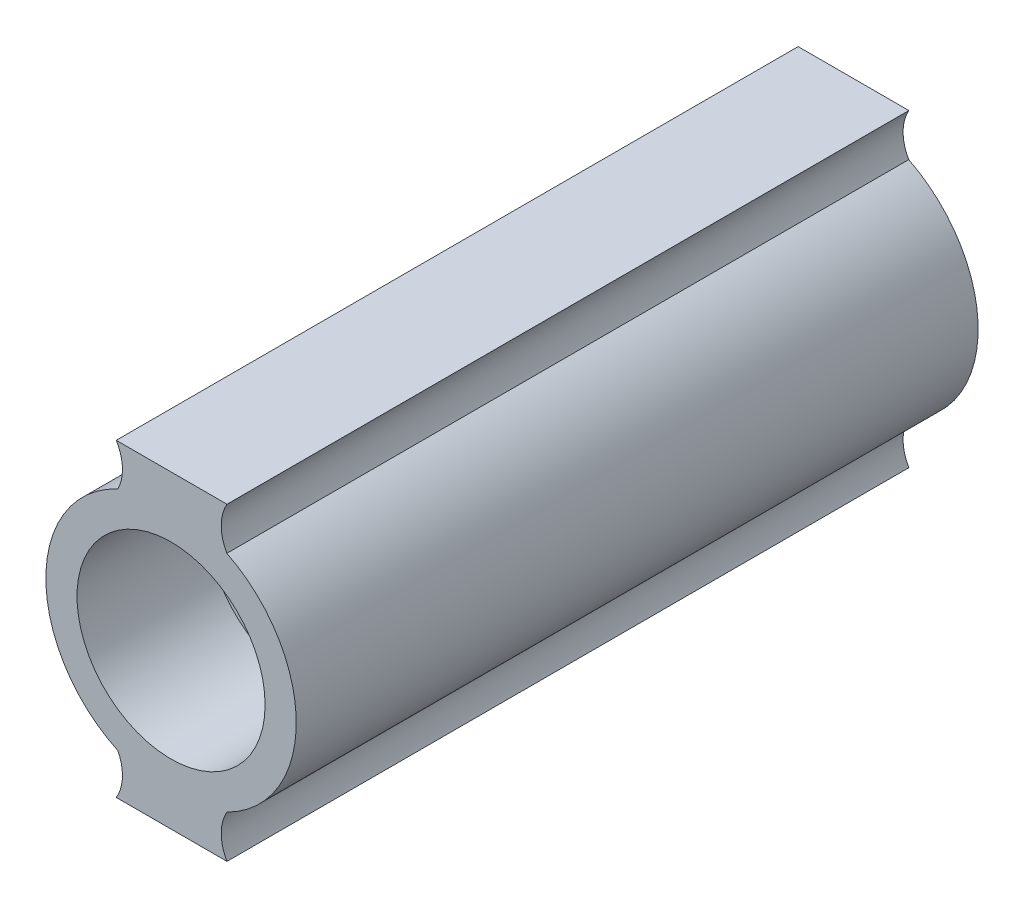
SolidWorks part; units mm, degrees
note: The reader was unsure of these and kept them because the rebuilt part matched: shared geometry of "Sketch1<3>", "Sketch1<6>", "Sketch1<7>".
material "ABS"
ref_plane "Front Plane" through (0, 0, 0) normal (0, 0, 1) x (1, 0, 0)
ref_plane "Top Plane" through (0, 0, 0) normal (0, 1, 0) x (1, 0, 0)
ref_plane "Right Plane" through (0, 0, 0) normal (1, 0, 0) x (0, 0, -1)
other "Center of Mass"
sketch "Sketch1" plane through (0, 0, 0) normal (0, 0, 1) x (1, 0, 0)
  circle A0 centre (-8.0877, 2.8885) radius 4.7625
  arc A1 (-0.1953, 6.0686) -> (-4.9075, 10.7808) centre (-8.0877, 2.8885) ccw
  arc A2 (-11.2679, 10.7808) -> (-15.9801, 6.0686) centre (-8.0877, 2.8885) ccw
  arc A3 (-15.9801, -0.2917) -> (-11.2679, -5.0039) centre (-8.0877, 2.8885) ccw
  arc A4 (-4.9075, -5.0039) -> (-0.1953, -0.2917) centre (-8.0877, 2.8885) ccw
  circle A5 centre (-8.0877, 2.8885) radius 14.0233
  circle A6 centre (-8.0877, 2.8885) radius 18.669
  circle A7 centre (-8.0877, 2.8885) radius 3.556
  ellipse E0 centre (0.2625, 2.8885) end of major axis (0.2625, -0.3246) minor radius 3.2067 (-0.1953, 6.0686) -> (-0.1953, -0.2917) ccw
  ellipse E1 centre (-8.0877, 11.2387) end of major axis (-4.8746, 11.2387) minor radius 3.2067 (-11.2679, 10.7808) -> (-4.9075, 10.7808) ccw
  ellipse E2 centre (-16.438, 2.8885) end of major axis (-16.438, 6.1016) minor radius 3.2067 (-15.9801, -0.2917) -> (-15.9801, 6.0686) ccw
  ellipse E3 centre (-8.0877, -5.4618) end of major axis (-11.3008, -5.4618) minor radius 3.2067 (-4.9075, -5.0039) -> (-11.2679, -5.0039) ccw
  ellipse E4 centre (-8.0877, -5.4618) end of major axis (-11.3008, -5.4618) minor radius 3.2067 (-11.2679, -5.0039) -> (-4.9075, -5.0039) ccw
  ellipse E5 centre (0.2625, 2.8885) end of major axis (0.2625, -0.3246) minor radius 3.2067 (-0.1953, -0.2917) -> (-0.1953, 6.0686) ccw
  ellipse E6 centre (-8.0877, 11.2387) end of major axis (-4.8746, 11.2387) minor radius 3.2067 (-4.9075, 10.7808) -> (-11.2679, 10.7808) ccw
  ellipse E7 centre (-16.438, 2.8885) end of major axis (-16.438, 6.1016) minor radius 3.2067 (-15.9801, 6.0686) -> (-15.9801, -0.2917) ccw
  dimension "D2" = 7.112
  dimension "D3" = 37.338
  dimension "D1" = 28.0467
extrude "Boss-Extrude1" add sketch "Sketch1" along normal blind 0.0025 contours E1 E6 | E2 E7 | E3 E4 | E0 E5
extrude "Boss-Extrude2" add sketch "Sketch1<3>" along normal blind 1.9812 contours E3 A4 E0 A1 E1 A2 E2 A3 A0 | A0 A7
sketch "Sketch1<3>" plane through (0, 0, 0) normal (0, 0, 1) x (1, 0, 0) same geometry as "Sketch1"
extrude "Boss-Extrude4" add sketch "Sketch1<6>" along normal blind 1.9812 contours A5 E7 A2 E6 A1 E5 A4 E4 A3 | A0
sketch "Sketch1<6>" plane through (0, 0, 0) normal (0, 0, 1) x (1, 0, 0) same geometry as "Sketch1"
extrude "Boss-Extrude5" add sketch "Sketch1<7>" along normal blind 21.4122 contours A6 A5
sketch "Sketch1<7>" plane through (0, 0, 0) normal (0, 0, 1) x (1, 0, 0) same geometry as "Sketch1"
sketch "Sketch2" plane through (0, 0, 21.4122) normal (0, 0, 1) x (1, 0, 0)
  line L8 (-8.0877, 2.8885) -> (10.5813, 2.8885)
  line L12 (-16.2578, 25.9505) -> (0.2522, 25.9505)
  line L13 (-16.2578, -20.1735) -> (0.2522, -20.1735)
  circle A0 centre (-8.0877, 2.8885) radius 18.669 construction
  arc A1 (1.6185, -13.059) -> (1.7452, -12.9812) centre (-8.0877, 2.8885) ccw
  arc A11 (-16.2578, 25.9505) -> (-16.0119, 19.7923) centre (-21.6826, 22.6498) cw
  arc A12 (0.2522, 25.9505) -> (0.2334, 19.6005) centre (5.742, 22.7592) ccw
  arc A19 (1.6185, -13.059) -> (1.7452, -12.9812) centre (3.56, -16.0784) cw
  arc A20 (-16.2578, -20.1735) -> (-16.0119, -14.0153) centre (-21.6826, -16.8729) ccw
  arc A21 (1.6185, -13.059) -> (1.7452, -12.9812) centre (-7.9548, 2.672) ccw
  arc A22 (0.2522, -20.1735) -> (0.2334, -13.8235) centre (5.742, -16.9823) cw
  dimension "D1" = 6.35
  dimension "D2" = 16.51
  dimension "D4" = 6.35
  dimension "D3" = 6.35
extrude "Boss-Extrude6" add sketch "Sketch2" against normal through all
sketch "Sketch3" plane through (0, 0, 0) normal (0, 0, -1) x (-1, 0, 0)
  line L1 (16.2578, 25.9505) -> (-0.2522, 25.9505)
  line L20 (16.2578, 25.9505) -> (-0.2522, 25.9505)
  line L23 (-0.2522, -20.1735) -> (16.2578, -20.1735)
  line L24 (-0.2522, -20.1735) -> (16.2578, -20.1735)
  circle A2 centre (8.0877, 2.8885) radius 4.826
  arc A3 (-0.2334, 19.6005) -> (-0.2334, -13.8235) centre (8.0877, 2.8885) ccw
  arc A59 (16.2578, 25.9505) -> (16.0119, 19.7923) centre (21.6826, 22.6498) ccw
  arc A63 (16.2578, 25.9505) -> (16.0119, 19.7923) centre (21.6826, 22.6498) ccw
  arc A65 (-0.2334, 19.6005) -> (-0.2334, -13.8235) centre (8.0877, 2.8885) ccw
  arc A74 (-0.2522, -20.1735) -> (-0.2334, -13.8235) centre (-5.742, -16.9823) ccw
  arc A75 (-0.2522, -20.1735) -> (-0.2334, -13.8235) centre (-5.742, -16.9823) ccw
  arc A76 (16.0119, -14.0153) -> (16.2578, -20.1735) centre (21.6826, -16.8729) ccw
  arc A77 (16.0119, -14.0153) -> (16.2578, -20.1735) centre (21.6826, -16.8729) ccw
  arc A78 (16.0119, -14.0153) -> (16.0119, 19.7923) centre (8.0877, 2.8885) ccw
  arc A79 (16.0119, -14.0153) -> (16.0119, 19.7923) centre (8.0877, 2.8885) ccw
  arc A80 (-0.2334, 19.6005) -> (-0.2522, 25.9505) centre (-5.742, 22.7592) ccw
  arc A81 (-0.2334, 19.6005) -> (-0.2522, 25.9505) centre (-5.742, 22.7592) ccw
  dimension "D2" = 9.652
  dimension "D1" = 0
extrude "Boss-Extrude7" add sketch "Sketch3" along normal blind 80.264
sketch "Sketch9" plane through (0, 0, 0) normal (0, 0, 1) x (1, 0, 0)
  circle A0 centre (-8.0877, 2.8885) radius 4.064
  dimension "D1" = 8.128
extrude "Cut-Extrude6" cut sketch "Sketch9" against normal blind 11.938
sketch "Sketch10" plane through (0, 0, -80.264) normal (0, 0, -1) x (-1, 0, 0)
  circle A1 centre (8.0877, 2.8885) radius 3.556
  dimension "D1" = 7.112
extrude "Cut-Extrude7" cut sketch "Sketch10" against normal blind 25.4
